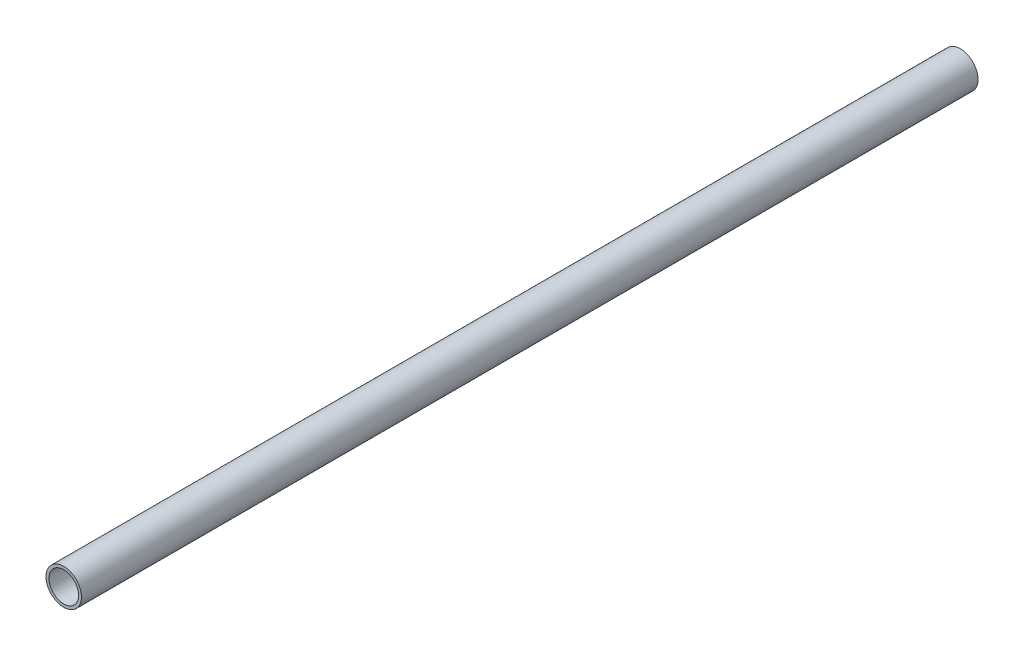
SolidWorks part; units mm, degrees
material "PVC Rigid"
ref_plane "Front Plane" through (0, 0, 0) normal (0, 0, 1) x (1, 0, 0)
ref_plane "Top Plane" through (0, 0, 0) normal (0, 1, 0) x (1, 0, 0)
ref_plane "Right Plane" through (0, 0, 0) normal (1, 0, 0) x (0, 0, -1)
sketch "Sketch1" plane through (0, 0, 0) normal (0, 0, 1) x (1, 0, 0)
  circle A0 centre (0, 0) radius 20.193
  circle A1 centre (0, 0) radius 24.13
  dimension "D1" = 48.26
  dimension "D2" = 40.386
extrude "Boss-Extrude1" add sketch "Sketch1" along normal blind 1219.2
ref_axis "Axis1" through (0, 0, 1247.2837) along (0, 0, -1)
